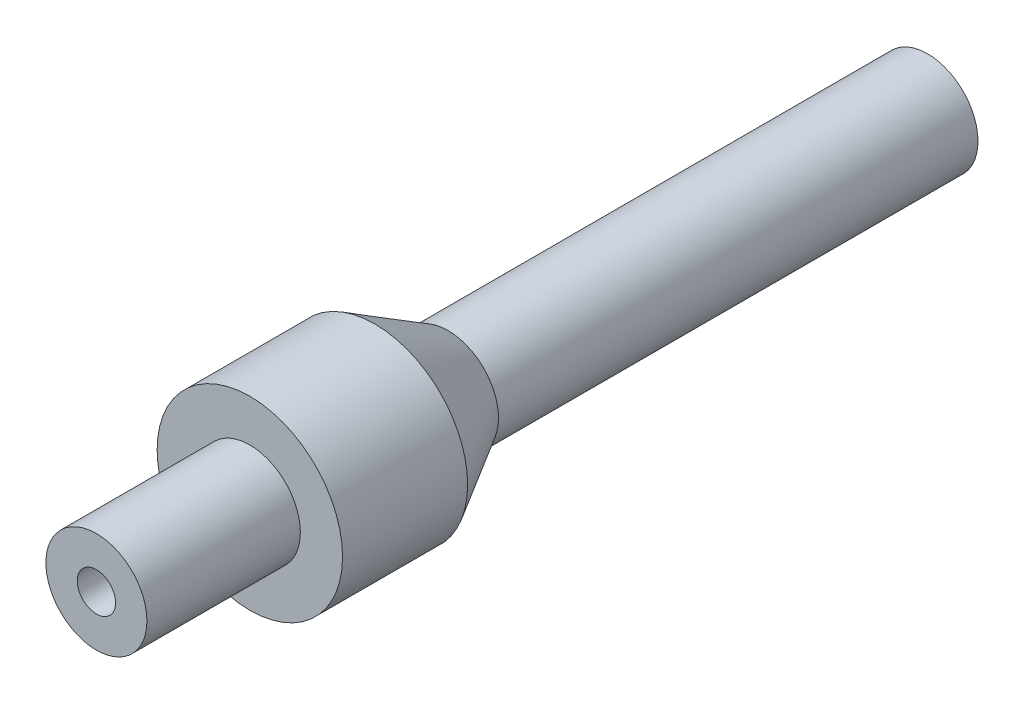
SolidWorks part; units mm, degrees
ref_plane "Top Plane" through (0, 0, 0) normal (0, 0, 1) x (1, 0, 0)
ref_plane "Right Plane" through (0, 0, 0) normal (0, 1, 0) x (1, 0, 0)
ref_plane "Front Plane" through (0, 0, 0) normal (1, 0, 0) x (0, 0, -1)
sketch "Sketch2" plane through (0, 0, 0) normal (0, 1, 0) x (1, 0, 0)
  line L0 (0, 0) -> (0, 65) construction
  line L1 (1.5, 0) -> (3.95, 0)
  line L2 (1.5, 0) -> (1.5, 65)
  line L3 (1.5, 65) -> (3.95, 65)
  line L4 (3.95, 65) -> (3.95, 17)
  line L5 (3.95, 17) -> (7.25, 17)
  line L6 (7.25, 17) -> (7.25, 12)
  line L7 (7.25, 12) -> (3.95, 12)
  line L8 (3.95, 12) -> (3.95, 0)
  line L9 (3.95, 0) -> (7.25, 0) construction
  line L10 (0, 65) -> (1.5, 65) construction
  dimension "D1" = 7.25
  dimension "D2" = 1.5
  dimension "D3" = 65
  dimension "D4" = 3.95
  dimension "D5" = 12
  dimension "D6" = 5
revolve "Revolve1" add sketch "Sketch2" angle 360 about L0
chamfer "Chamfer1" distance 10.5 angle 30 1 edges at (3.95, 0, -17) first distance on face at (3.95, 0, -65)
